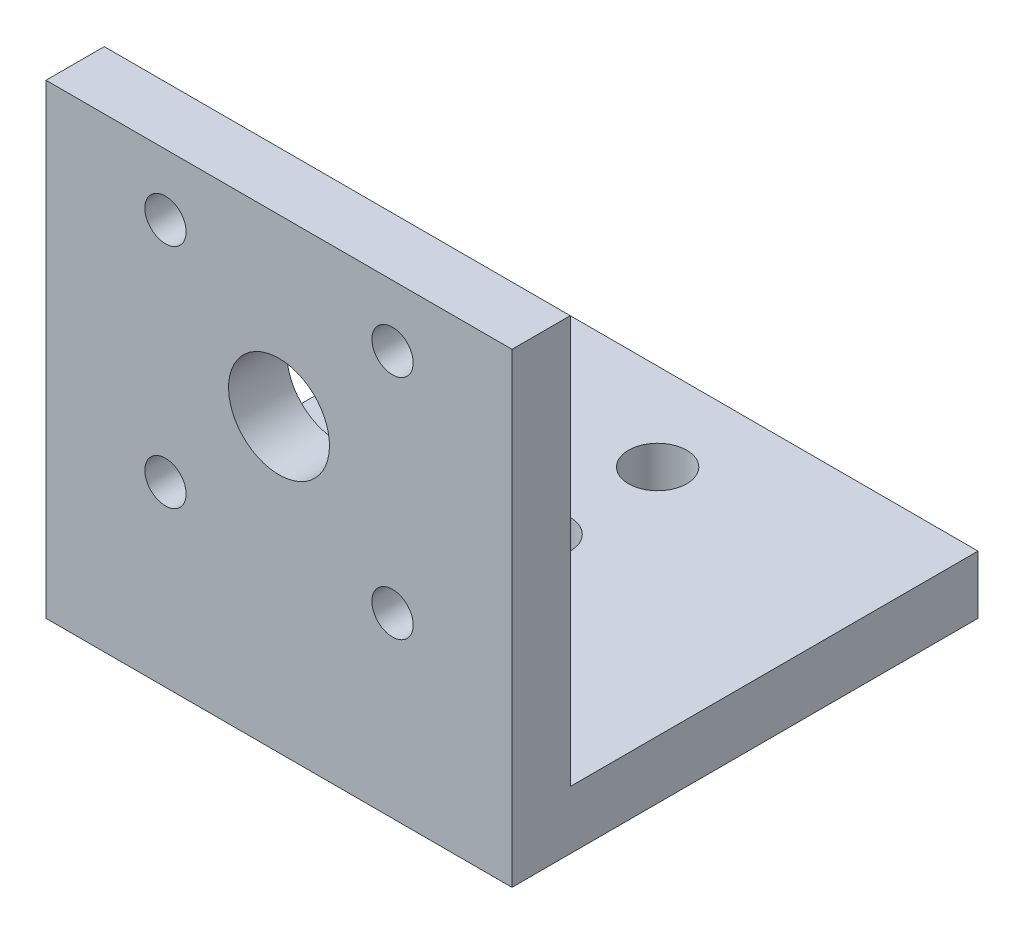
SolidWorks part; units mm, degrees
ref_plane "Front Plane" through (0, 0, 0) normal (0, 0, 1) x (1, 0, 0)
ref_plane "Top Plane" through (0, 0, 0) normal (0, 1, 0) x (1, 0, 0)
ref_plane "Right Plane" through (0, 0, 0) normal (1, 0, 0) x (0, 0, -1)
sketch "Sketch1" plane through (0, 0, 0) normal (1, 0, 0) x (0, 0, -1)
  line L0 (0, 0) -> (0, -44.45)
  line L1 (0, -44.45) -> (44.45, -44.45)
  line L2 (-6.35, 0) -> (-6.35, -50.8)
  line L3 (-6.35, -50.8) -> (44.45, -50.8)
  line L4 (-6.35, 0) -> (0, 0)
  line L5 (44.45, -44.45) -> (44.45, -50.8)
  dimension "D2" = 50.8
  dimension "D3" = 50.8
  dimension "D1" = 6.35
extrude "Boss-Extrude1" add sketch "Sketch1" along normal blind 50.8
sketch "Sketch2" plane through (0, 0, 0) normal (0, 0, -1) x (-1, 0, 0)
  line L1 (-50.8, 0) -> (0, 0) construction
  line L2 (-13.0256, -6.6756) -> (-37.7744, -6.6756) construction
  line L3 (-50.8, -44.45) -> (-50.8, 0) construction
  circle A0 centre (-13.0256, -6.6756) radius 2.25
  circle A1 centre (-13.0256, -31.4244) radius 2.25
  circle A2 centre (-37.7744, -31.4244) radius 2.25
  circle A3 centre (-37.7744, -6.6756) radius 2.25
  circle A4 centre (-25.4, -19.05) radius 5.5
  point P3 (-50.8, -22.225)
  point P12 (-25.4, -19.05)
  dimension "D1" = 17.5
  dimension "D2" = 4.5
  dimension "D7" = 11
  dimension "D4" = 25.4
  dimension "D5" = 19.05
  dimension "D6" = 0
  dimension "D3" = 4
extrude "Cut-Extrude1" cut sketch "Sketch2" against normal up to next
sketch "Sketch4" plane through (0, -44.45, 0) normal (0, 1, 0) x (1, 0, 0)
  line L0 (0, 44.45) -> (0, 0) construction
  line L1 (50.8, 44.45) -> (0, 44.45) construction
  line L2 (50.8, 44.45) -> (50.8, 0) construction
  circle A0 centre (25.4, 34.925) radius 3.175
  circle A1 centre (25.4, 22.225) radius 3.175
  dimension "D1" = 6.35
  dimension "D2" = 6.35
  dimension "D3" = 25.4
  dimension "D4" = 22.225
  dimension "D5" = 9.525
  dimension "D6" = 25.4
extrude "Cut-Extrude2" cut sketch "Sketch4" against normal up to next
hole_wizard "CSK for M4 SFHCS1" positions "Sketch6" profile "Sketch5" countersink size "M4" standard "ANSI Metric" end condition up to next
sketch "Sketch6" plane through (20.3784, 4.8579, 0) normal (0, 0, 1) x (1, 0, 0)
  point P0 (-7.3527, -11.5335)
  point P3 (17.396, -11.5335)
  point P6 (17.396, -36.2823)
  point P9 (-7.3527, -36.2823)
sketch "Sketch5" plane through (13.0256, -6.6756, 0) normal (1, 0, 0) x (0, 1, 0)
  line L0 (0, 0) -> (0, 6.35)
  line L1 (0, 6.35) -> (2.15, 6.35)
  line L2 (2.15, 6.35) -> (2.15, 2.33)
  line L3 (2.15, 2.33) -> (4.48, 0)
  line L5 (4.48, 0) -> (0, 0)
  line L6 (-2.15, 2.33) -> (-4.48, 0) construction
  line L11 (0, -6.35) -> (0, 107.95) construction
  dimension "Thru Hole Dia." = 4.3
  dimension "Thru Hole Depth" = 6.35
  dimension "Near C'Sink Dia." = 8.96
  dimension "Near C'Sink Angle" = 90
ref_plane "Plane1" through (50.8, -44.45, -44.45) normal (0, 1, 0) x (1, 0, 0)
